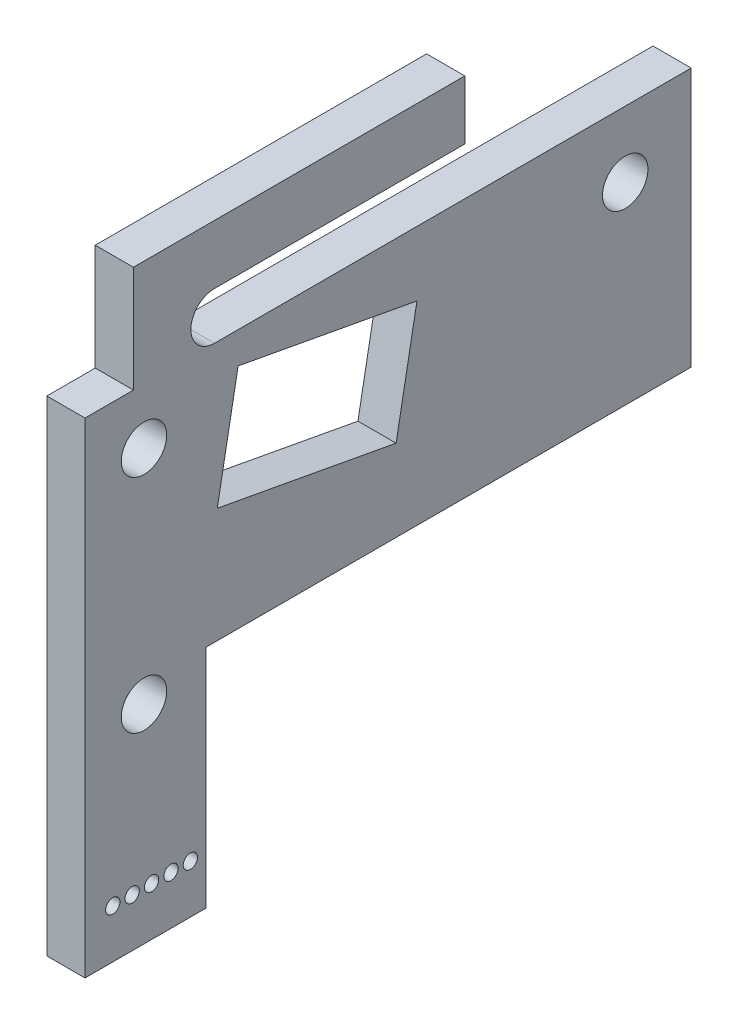
SolidWorks part; units mm, degrees
material "Hardboard"
ref_plane "Front Plane" through (0, 0, 0) normal (0, 0, 1) x (1, 0, 0)
ref_plane "Top Plane" through (0, 0, 0) normal (0, 1, 0) x (1, 0, 0)
ref_plane "Right Plane" through (0, 0, 0) normal (1, 0, 0) x (0, 0, -1)
sketch "Sketch1" plane through (0, 0, 0) normal (1, 0, 0) x (0, 0, -1)
  line L0 (-56.5904, 6.9096) -> (-51.5186, 6.9096)
  line L1 (-56.5904, 6.9096) -> (-56.5904, -43.8904)
  line L2 (-56.5904, -43.8904) -> (-43.8904, -43.8904)
  line L3 (-43.8904, -43.8904) -> (-43.8904, -20.2221)
  line L4 (-43.8904, -20.2221) -> (6.9096, -20.2221)
  line L5 (6.9096, -20.2221) -> (6.9096, 6.9096)
  line L6 (0, 6.9096) -> (0, 0) construction
  line L7 (6.9096, 0) -> (0, 0) construction
  line L8 (-40.5479, 3.6124) -> (-21.8156, 0.1475)
  line L9 (-40.5479, 3.6124) -> (-42.7334, -8.2033)
  line L10 (-21.8156, 0.1475) -> (-24.0012, -11.6682)
  line L11 (-42.7334, -8.2033) -> (-24.0012, -11.6682)
  line L12 (-45.553, -38.8104) -> (-47.585, -38.8104) construction
  line L13 (-43.0182, 11.8731) -> (-16.804, 11.8731)
  line L14 (-16.804, 11.8731) -> (-16.804, 18.0537)
  line L15 (-16.804, 18.0537) -> (-51.5186, 18.0537)
  line L16 (-51.5186, 18.0537) -> (-51.5186, 6.9096)
  line L17 (-43.0182, 6.9096) -> (6.9096, 6.9096)
  line L18 (-43.0916, -6.1748) -> (-43.04, 6.5251) construction
  circle A0 centre (0, 0) radius 2.3813
  circle A1 centre (-45.553, -38.8104) radius 0.75
  circle A2 centre (-47.585, -38.8104) radius 0.75
  circle A3 centre (-49.617, -38.8104) radius 0.75
  circle A4 centre (-51.649, -38.8104) radius 0.75
  circle A5 centre (-50.4101, -22.1372) radius 2.3812
  circle A6 centre (-50.4101, 1.0794) radius 2.3812
  circle A7 centre (-53.681, -38.8104) radius 0.75
  arc A8 (-43.0182, 6.9096) -> (-43.0182, 11.8731) centre (-43.0182, 9.3913) cw
  dimension "D1" = 4.7625
  dimension "D2" = 1.5
  dimension "D3" = 5.08
  dimension "D5" = 2.032
  dimension "D6" = 19.05
  dimension "D4" = 5
extrude "Boss-Extrude1" add sketch "Sketch1" along normal mid plane 4
